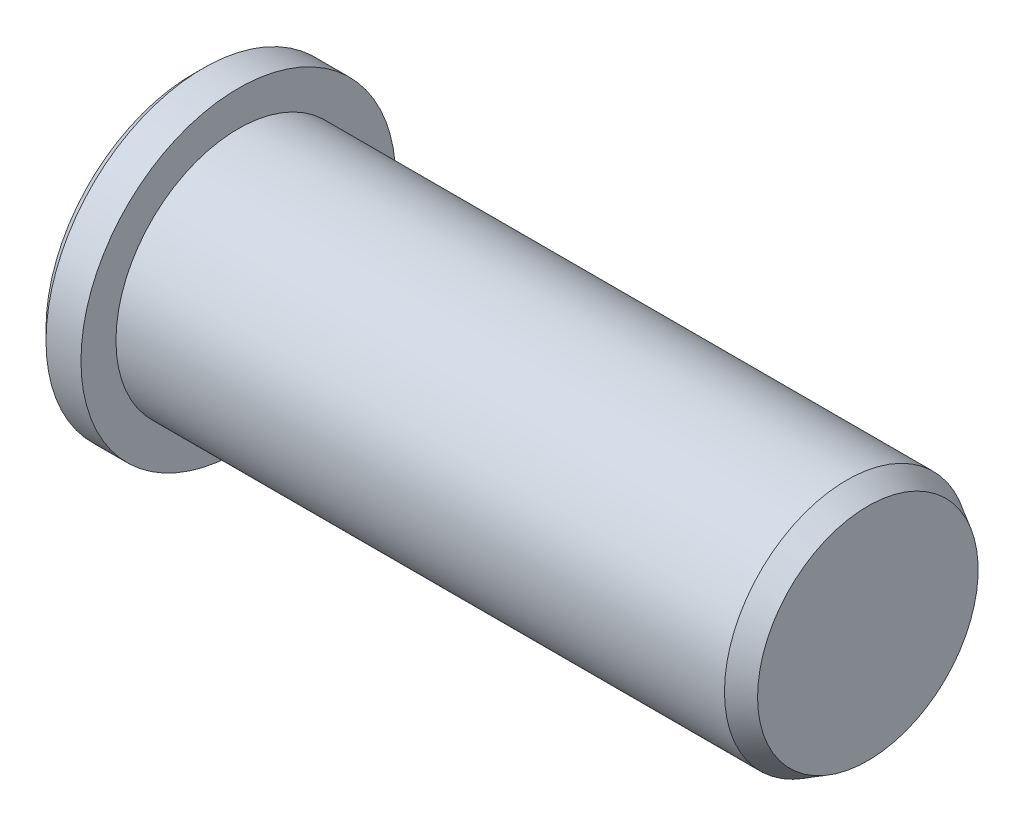
SolidWorks part; units mm, degrees
ref_plane "Front Plane" through (0, 0, 0) normal (0, 0, 1) x (1, 0, 0)
ref_plane "Top Plane" through (0, 0, 0) normal (0, 1, 0) x (1, 0, 0)
ref_plane "Right Plane" through (0, 0, 0) normal (1, 0, 0) x (0, 0, -1)
sketch "BodySke" plane through (0, 0, 0) normal (0, 0, 1) x (1, 0, 0)
  line L0 (0, 0) -> (231.5186, 0) construction
  line L1 (0, 0) -> (0, 42)
  line L2 (0, 42) -> (3, 45)
  line L3 (3, 45) -> (13, 45)
  line L4 (13, 45) -> (13, 35)
  line L5 (13, 35) -> (187, 35)
  line L6 (187, 35) -> (193, 31.5359)
  line L7 (193, 31.5359) -> (193, 0)
  line L8 (0, 0) -> (193, 0)
  circle A0 centre (177, 0) radius 6.5 construction
  dimension "Hole_dia" = 13
  dimension "Head_dia" = 90
  dimension "Head_height" = 13
  dimension "Diameter" = 70
  dimension "Chamfer_width" = 3
  dimension "Chamfer_angle" = 45
  dimension "Length" = 180
  dimension "End_chamfer_angle" = 30
  dimension "End_chamfer_width" = 6
  dimension "Hole_height" = 16
revolve "BaseBody" add sketch "BodySke" angle 360 about L0
sketch "HoleSke" plane through (0, 0, 0) normal (0, 0, 1) x (1, 0, 0)
  line L0 (0, 0) -> (194.6145, 0) construction
  line L1 (0, 42) -> (0, -42) construction
  line L2 (0, 0) -> (231.5186, 0) construction
  circle A0 centre (177, 0) radius 6.5 construction
  circle A1 centre (177, 0) radius 6.5
extrude "Hole" [suppressed] cut sketch "HoleSke" against normal through all and the other way through all
